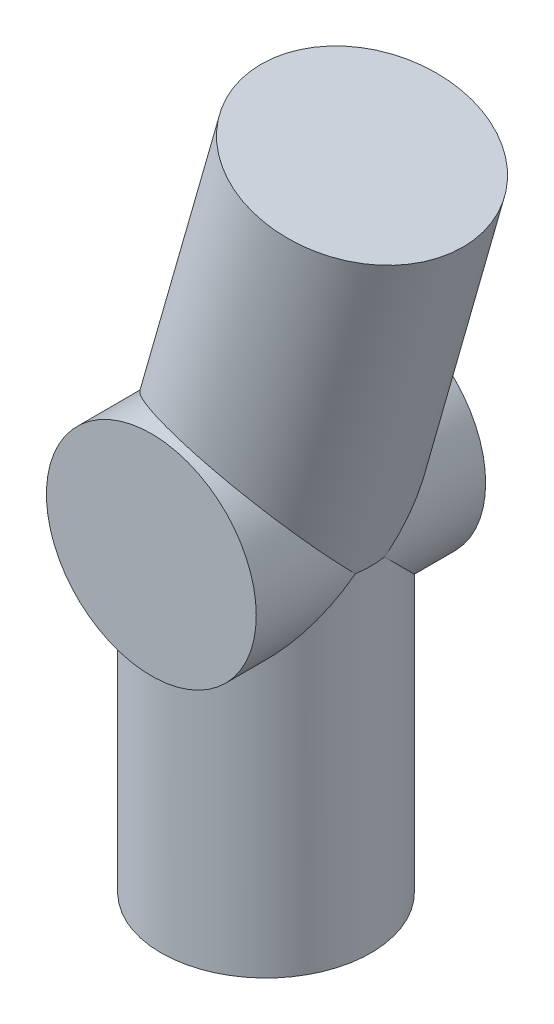
SolidWorks part; units mm, degrees
ref_plane "Front Plane" through (0, 0, 0) normal (0, 0, 1) x (1, 0, 0)
ref_plane "Top Plane" through (0, 0, 0) normal (0, 1, 0) x (1, 0, 0)
ref_plane "Right Plane" through (0, 0, 0) normal (1, 0, 0) x (0, 0, -1)
sketch "Croquis1" plane through (0, 0, 0) normal (0, 0, 1) x (1, 0, 0)
  circle A0 centre (0, 0) radius 3.1
  circle A1 centre (0, 0) radius 3.6
  circle A2 centre (0, 0) radius 2.475
  dimension "D1" = 4.95
  dimension "D2" = 6.2
  dimension "D3" = 7.2
extrude "Saliente-Extruir1" add sketch "Croquis1" along normal blind 7.87 contours A1 A0 | A1 region at (-3.4982, 0, 0)
extrude "Saliente-Extruir2" add sketch "Croquis1<3>" along normal offset from surface (6.17 mm away) 0.85 from offset 0.85 contours A0 A2 region at (-3.0123, 0, 0) up to face at (3.6, 0, 7.87)
sketch "Croquis1<3>" plane through (0, 0, 0) normal (0, 0, 1) x (1, 0, 0) same geometry as "Croquis1"
ref_plane "Plano1" through (0, -4, 0) normal (0, 1, 0) x (1, 0, 0)
sketch "Croquis2" plane through (0, -4, 0) normal (0, 1, 0) x (1, 0, 0)
  line L0 (-1.01, -6.1945) -> (-1.01, -4.945)
  line L1 (1.01, -6.1945) -> (1.01, -4.945)
  line L2 (-2.2595, -2.925) -> (-1.01, -2.925)
  line L3 (2.2595, -4.945) -> (1.01, -4.945)
  line L4 (-1.01, -4.945) -> (-2.2595, -4.945)
  line L5 (1.01, -2.925) -> (1.01, -1.6755)
  line L6 (-1.01, -2.925) -> (-1.01, -1.6755)
  line L7 (1.01, -2.925) -> (2.2595, -2.925)
  arc A0 (-1.01, -6.1945) -> (1.01, -6.1945) centre (0, -3.935) ccw
  arc A1 (-1.7125, -7.1016) -> (1.8067, -7.0488) centre (0, -3.935) ccw
  arc A2 (-1.7125, -7.1016) -> (-3.1138, -5.7417) centre (-3.94, -7.995) ccw
  arc A3 (-3.1666, -2.2225) -> (-1.8067, -0.8212) centre (-4.06, 0.005) ccw
  arc A4 (1.7125, -0.7684) -> (3.1138, -2.1283) centre (3.94, 0.125) ccw
  arc A5 (3.1666, -5.6475) -> (1.8067, -7.0488) centre (4.06, -7.875) ccw
  arc A6 (3.1666, -5.6475) -> (3.1138, -2.1283) centre (0, -3.935) ccw
  arc A7 (1.7125, -0.7684) -> (-1.8067, -0.8212) centre (0, -3.935) ccw
  arc A8 (-3.1666, -2.2225) -> (-3.1138, -5.7417) centre (0, -3.935) ccw
  arc A9 (2.2595, -4.945) -> (2.2595, -2.925) centre (0, -3.935) ccw
  arc A10 (1.01, -1.6755) -> (-1.01, -1.6755) centre (0, -3.935) ccw
  arc A11 (-2.2595, -2.925) -> (-2.2595, -4.945) centre (0, -3.935) ccw
  circle A12 centre (0, -3.935) radius 3.6
  dimension "D2" = 4.95
  dimension "D3" = 7.2
  dimension "D4" = 4.8
  dimension "D1" = 3.935
  dimension "D5" = 3.94
  dimension "D6" = 4.06
  dimension "D8" = 2.02
  dimension "D9" = 1.01
  dimension "D10" = 2.02
  dimension "D11" = 1.01
  dimension "D7" = 4
extrude "Saliente-Extruir3" add sketch "Croquis2" along normal up to surface (0.8334 mm away) contours A3 A8 A2 A1 A5 A6 A4 A7 A11 L2 L6 A10 L5 L7 A9 L3 L1 A0 L0 L4 | A12 region at (-2.1977, -4, 6.1996) up to face at (3.6, 0, 7.87)
extrude "Saliente-Extruir4" add sketch "Croquis2<3>" against normal blind 8 contours A3 A8 A2 A1 A5 A6 A4 A7 A11 L2 L6 A10 L5 L7 A9 L3 L1 A0 L0 L4 | A12 region at (-2.1977, -4, 6.1996)
sketch "Croquis2<3>" plane through (0, -4, 0) normal (0, 1, 0) x (1, 0, 0) same geometry as "Croquis2"
sketch "Croquis5" plane through (0, 0, 0) normal (1, 0, 0) x (0, 0, -1)
  line L0 (0, 0) -> (-7.87, 0) construction
  line L1 (-7.87, 3.6) -> (-7.87, -3.6) construction
ref_plane "Plano3" through (0, 0, 0) normal (-0.2745, -0.9616, 0) x (0, 0, 1)
ref_plane "Plano4" through (1.0979, 3.8464, 0) normal (-0.2745, -0.9616, 0) x (0, 0, 1)
sketch "Croquis7" plane through (1.0979, 3.8464, 0) normal (-0.2745, -0.9616, 0) x (0, 0, 1)
  line L0 (2.925, -2.2595) -> (2.925, -1.01)
  line L1 (4.945, -2.2595) -> (4.945, -1.01)
  line L2 (1.6755, 1.01) -> (2.925, 1.01)
  line L3 (6.1945, -1.01) -> (4.945, -1.01)
  line L4 (2.925, -1.01) -> (1.6755, -1.01)
  line L5 (4.945, 1.01) -> (4.945, 2.2595)
  line L6 (2.925, 1.01) -> (2.925, 2.2595)
  line L7 (4.945, 1.01) -> (6.1945, 1.01)
  line L8 (7.87, -3.6) -> (7.87, 3.6) construction
  arc A0 (2.925, -2.2595) -> (4.945, -2.2595) centre (3.935, 0) ccw
  arc A1 (2.2225, -3.1666) -> (5.7417, -3.1138) centre (3.935, 0) ccw
  arc A2 (2.2225, -3.1666) -> (0.8212, -1.8067) centre (-0.005, -4.06) ccw
  arc A4 (5.6475, 3.1666) -> (7.0488, 1.8067) centre (7.875, 4.06) ccw
  arc A6 (7.1016, -1.7125) -> (7.0488, 1.8067) centre (3.935, 0) ccw
  arc A7 (5.6475, 3.1666) -> (2.1283, 3.1138) centre (3.935, 0) ccw
  arc A8 (0.7684, 1.7125) -> (0.8212, -1.8067) centre (3.935, 0) ccw
  arc A9 (6.1945, -1.01) -> (6.1945, 1.01) centre (3.935, 0) ccw
  arc A10 (4.945, 2.2595) -> (2.925, 2.2595) centre (3.935, 0) ccw
  arc A11 (1.6755, 1.01) -> (1.6755, -1.01) centre (3.935, 0) ccw
  arc A12 (7.1016, -1.7125) -> (5.7417, -3.1138) centre (7.995, -3.94) ccw
  arc A13 (2.2225, -3.1666) -> (0.8212, -1.8067) centre (-0.005, -4.06) ccw
  arc A14 (0.7684, 1.7125) -> (2.1283, 3.1138) centre (-0.125, 3.94) ccw
  circle A15 centre (3.935, 0) radius 3.6
  dimension "D1" = 4.95
  dimension "D2" = 7.2
  dimension "D3" = 4.8
  dimension "D13" = 2.4
  dimension "D4" = 3.94
  dimension "D5" = 4.06
  dimension "D6" = 2.02
  dimension "D7" = 1.01
  dimension "D8" = 2.02
  dimension "D9" = 1.01
  dimension "D10" = 3.935
  dimension "D11" = 3.94
  dimension "D12" = 4.06
  dimension "D14" = 4
extrude "Saliente-Extruir5" add sketch "Croquis7" along normal up to surface (0.8334 mm away) contours A12 A1 A2 A8 A14 A7 A4 A6 | A15 up to face at (0, -3.6, 3.935)
extrude "Saliente-Extruir6" add sketch "Croquis7<3>" against normal blind 8 contours A14 A8 A2 A1 A12 A6 A4 A7 A11 L2 L6 A10 L5 L7 A9 L3 L1 A0 L0 L4 | A15 region at (3.2755, 3.2248, 1.7373)
sketch "Croquis7<3>" plane through (1.0979, 3.8464, 0) normal (-0.2745, -0.9616, 0) x (0, 0, 1) same geometry as "Croquis7"
equation "\"D9@Croquis2\"=\"D8@Croquis2\"/2"
equation "\"D11@Croquis2\"=\"D10@Croquis2\"/2"
equation "\"angle\"= 163"
